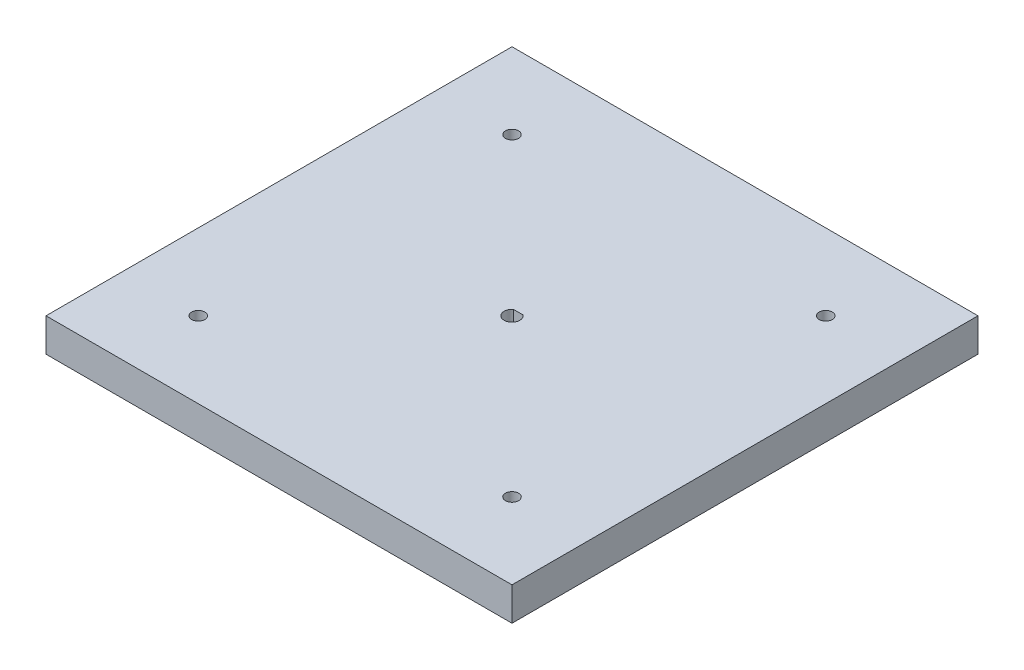
SolidWorks part; units mm, degrees
ref_plane "Front Plane" through (0, 0, 0) normal (0, 0, 1) x (1, 0, 0)
ref_plane "Top Plane" through (0, 0, 0) normal (0, 1, 0) x (1, 0, 0)
ref_plane "Right Plane" through (0, 0, 0) normal (1, 0, 0) x (0, 0, -1)
sketch "Sketch2" plane through (0, 0, 0) normal (0, 1, 0) x (1, 0, 0)
  line L0 (-1.8, 2.4) -> (1.8, 2.4)
  line L1 (-88.9, -88.9) -> (88.9, -88.9)
  line L2 (-88.9, -88.9) -> (-88.9, 88.9)
  line L3 (-88.9, 88.9) -> (88.9, 88.9)
  line L4 (88.9, -88.9) -> (88.9, 88.9)
  line L5 (-88.9, -88.9) -> (88.9, 88.9) construction
  line L6 (-88.9, 88.9) -> (88.9, -88.9) construction
  arc A1 (-1.8, 2.4) -> (1.8, 2.4) centre (0, 0) ccw
  arc A2 (1.8, 2.4) -> (-1.8, 2.4) centre (0, 0) ccw construction
  point P0 (0, 0)
  dimension "D3" = 6
  dimension "D1" = 177.8
  dimension "D2" = 177.8
  dimension "D4" = 2.4
extrude "Boss-Extrude1" add sketch "Sketch2" along normal mid plane 12.7
sketch "Sketch3" plane through (0, -6.35, 0) normal (0, -1, 0) x (1, 0, 0)
  circle A0 centre (-59.8566, -59.8566) radius 2.5 construction
  circle A1 centre (59.8566, -59.8566) radius 2.5 construction
  circle A2 centre (59.8566, 59.8566) radius 2.5 construction
  circle A3 centre (-59.8566, 59.8566) radius 2.5 construction
  circle A4 centre (-59.8566, -59.8566) radius 2.5
  circle A5 centre (59.8566, -59.8566) radius 2.5
  circle A6 centre (59.8566, 59.8566) radius 2.5
  circle A7 centre (-59.8566, 59.8566) radius 2.5
extrude "Cut-Extrude1" cut sketch "Sketch3" against normal up to surface (12.7 mm away) up to face at (0, 6.35, 0)
